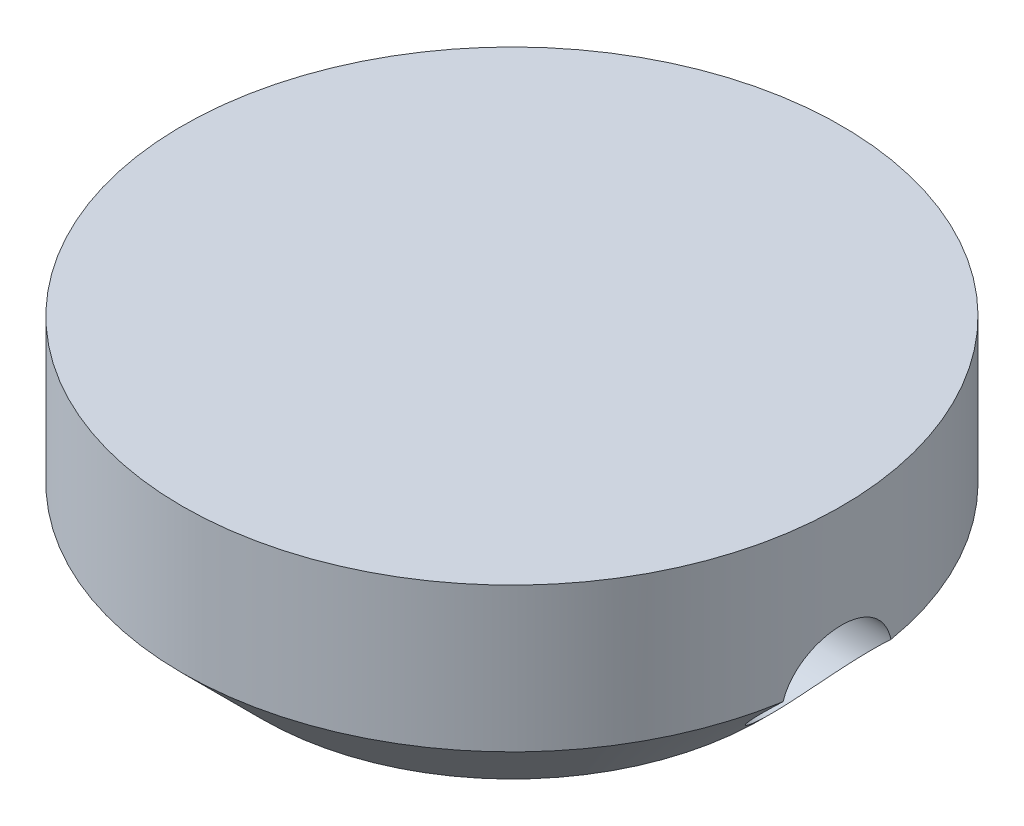
SolidWorks part; units mm, degrees
ref_plane "Front Plane" through (0, 0, 0) normal (0, 0, 1) x (1, 0, 0)
ref_plane "Top Plane" through (0, 0, 0) normal (0, 1, 0) x (1, 0, 0)
ref_plane "Right Plane" through (0, 0, 0) normal (1, 0, 0) x (0, 0, -1)
sketch "Sketch1" plane through (0, 0, 0) normal (0, 0, 1) x (1, 0, 0)
  line L0 (0, 2.0519) -> (0, -2.0519) construction
  line L1 (0, 3.3632) -> (-11.5, 3.3632)
  line L2 (-11.5, 3.3632) -> (-11.5, -1.6768)
  line L3 (-11.5, -1.6768) -> (0, -1.6768)
  line L4 (0, -1.6768) -> (0, 0.4232)
  line L5 (0, 0.4232) -> (-9.5, 0.4232)
  line L6 (-9.5, 0.4232) -> (-9.5, 3.1632)
  line L7 (-9.5, 3.1632) -> (0, 3.1632)
  line L8 (0, 3.1632) -> (0, 3.3632)
  point P4 (0, 0)
  dimension "D1" = 0.2
  dimension "D2" = 2
  dimension "D3" = 2.1
  dimension "D4" = 11.5
  dimension "D5" = 5.04
revolve "Revolve1" add sketch "Sketch1" angle 360 about L0
ref_plane "Plane1" through (-11.5, 0, 0) normal (-1, 0, 0) x (0, 0, 1)
ref_plane "Plane2" through (0, 0.4232, 0) normal (0, 1, 0) x (1, 0, 0)
ref_plane "Plane3" through (11.5, 0, 0) normal (1, 0, 0) x (0, 0, -1)
sketch "Sketch5" plane through (11.5, 0, 0) normal (1, 0, 0) x (0, 0, -1)
  line L0 (10.45, 0.4232) -> (-10.45, 0.4232) construction
  circle A0 centre (0, 1.9482) radius 0.75
  dimension "D1" = 1.5
  dimension "D2" = 1.525
fillet "Fillet3" radius 0.8 1 edges at (0, 0.4232, 9.5)
fillet "Fillet4" radius 1 1 edges at (0, 3.1632, 9.5)
sketch "Sketch6" plane through (0, -1.6768, 0) normal (0, -1, 0) x (1, 0, 0)
  circle A0 centre (0, 0) radius 2.45
  dimension "D1" = 4.9
extrude "Boss-Extrude2" add sketch "Sketch6" along normal blind 2.8 contours A0
sketch "Sketch7" plane through (0, -4.4768, 0) normal (0, -1, 0) x (1, 0, 0)
  circle A0 centre (0, 0) radius 1.95
  dimension "D1" = 3.9
extrude "Cut-Extrude3" [suppressed] cut sketch "Sketch7" against normal up to surface (4.9 mm away)
ref_plane "Plane4" through (0, 0, 0) normal (0, 0, 1) x (1, 0, 0)
chamfer "Chamfer2" distance 9.05 angle 45 1 edges at (0, -1.6768, -2.45)
fillet "Fillet5" [suppressed] radius 1
fillet "Fillet6" [suppressed] radius 1
extrude "Cut-Extrude4" [suppressed] cut sketch "Sketch5" against normal up to next
sketch "Sketch9" plane through (0, 0.4232, 0) normal (0, 1, 0) x (1, 0, 0)
  circle A1 centre (0, 0) radius 1.95
  circle A2 centre (0, 0) radius 1.95
  dimension "D1" = 0
sketch "Sketch8" plane through (11.5, 0, 0) normal (1, 0, 0) x (0, 0, -1)
  line L1 (-8.7, -4.4768) -> (8.7, -4.4768) construction
  circle A0 centre (0, -2.1768) radius 1.95
  dimension "D1" = 3.9
  dimension "D2" = 2.3
sketch "Sketch10" plane through (0, 0, 0) normal (0, 0, 1) x (1, 0, 0)
  line L2 (0, 0.4232) -> (0, 0.3232)
  line L3 (1.95, 0.4232) -> (-1.95, 0.4232) construction
  line L4 (2.5, -2.1768) -> (11.5, -2.1768)
  line L5 (11.5, -4.1268) -> (11.5, -0.2268) construction
  arc A0 (0, 0.3232) -> (2.5, -2.1768) centre (2.5, 0.3232) ccw
  dimension "D1" = 2.5
sweep "Cut-Sweep1" cut profiles "Sketch9" path "Sketch10"
equation "\"top_thickness\"= 0.2mm"
equation "\"wall_thickness\"= 2mm"
equation "\"diameter\"= 23mm"
equation "\"height\"= 7.2mm * .7"
equation "\"tube_outer_dia\"= 4.9mm"
equation "\"tube_inner_dia\"= 3.9mm"
equation "\"tube_height\"= 1.0mm"
equation "\"outlet_dia\"= 1.5mm"
equation "\"D1@Sketch1\"=\"top_thickness\""
equation "\"D2@Sketch1\"=\"wall_thickness\""
equation "\"D3@Sketch1\"=\"back_thickness\""
equation "\"D4@Sketch1\"=\"diameter\"/2"
equation "\"D5@Sketch1\"=\"height\""
equation "\"D1@Sketch5\"=\"outlet_dia\""
equation "\"D2@Sketch5\"=.7*\"outlet_dia\"/2 + \"tube_height\""
equation "\"internal_volume\"= ( 3.14 * ( \"diameter\" - 2 * \"wall_thickness\" ) ^ 2 / 4 ) * ( \"height\" - \"back_thickness\" - \"top_thickness\" )"
equation "\"D1@Sketch6\"=\"tube_outer_dia\""
equation "\"D1@Sketch7\"=\"tube_inner_dia\""
equation "\"back_thickness\"= 3mm * .7"
equation "\"D1@Sketch8\"=\"tube_inner_dia\""
